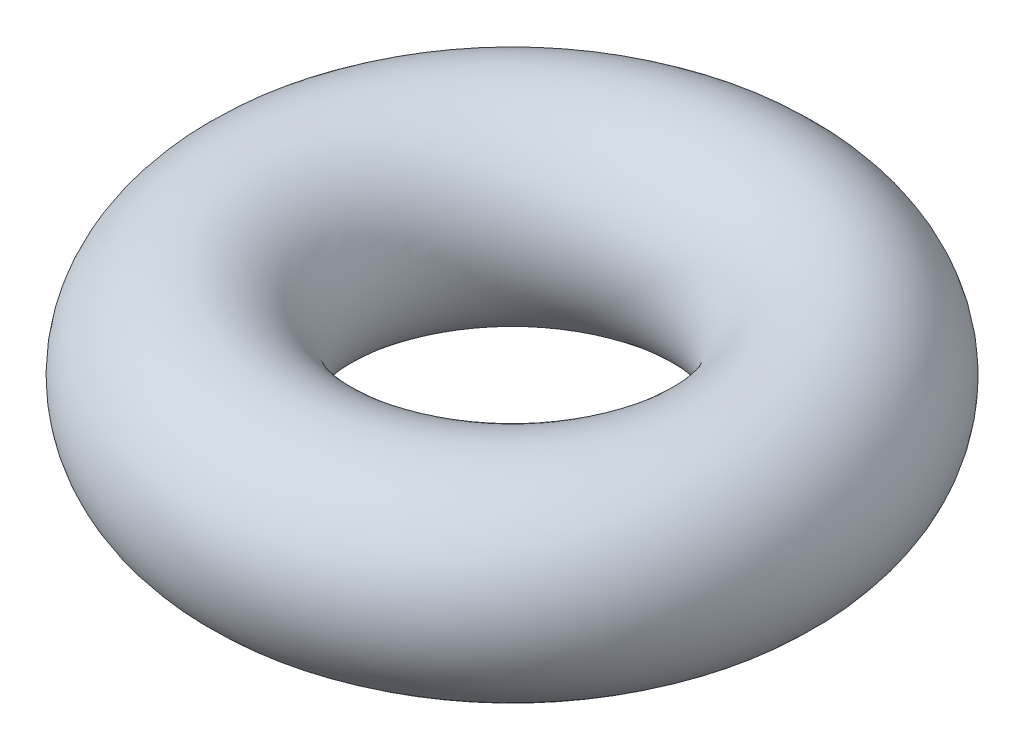
SolidWorks part; units mm, degrees
material "Silicon Rubber"
ref_plane "Front Plane" through (0, 0, 0) normal (0, 0, 1) x (1, 0, 0)
ref_plane "Top Plane" through (0, 0, 0) normal (0, 1, 0) x (1, 0, 0)
ref_plane "Right Plane" through (0, 0, 0) normal (1, 0, 0) x (0, 0, -1)
ref_axis "CentralAxis" through (0, 0.55, 0) along (0, -1, 0)
sketch "MainBodyS" plane through (0, 0, 0) normal (0, 0, 1) x (1, 0, 0)
  line L0 (0, 0) -> (1.4, 0) construction
  line L1 (0, 0) -> (0, -1) construction
  circle A0 centre (1.4, 0) radius 0.6
  point P3 (2, 0)
  point P6 (-2, 0)
  point P7 (-0.8, 0)
  point P8 (0.8, 0)
  dimension "Dia" = 1.2
  dimension "RefRevolve" = 1
  dimension "RevolveDia" = 2.8
  dimension "OD" = 4
  dimension "ID" = 1.6
revolve "MAIN BODY" add sketch "MainBodyS" angle 360 about L1
